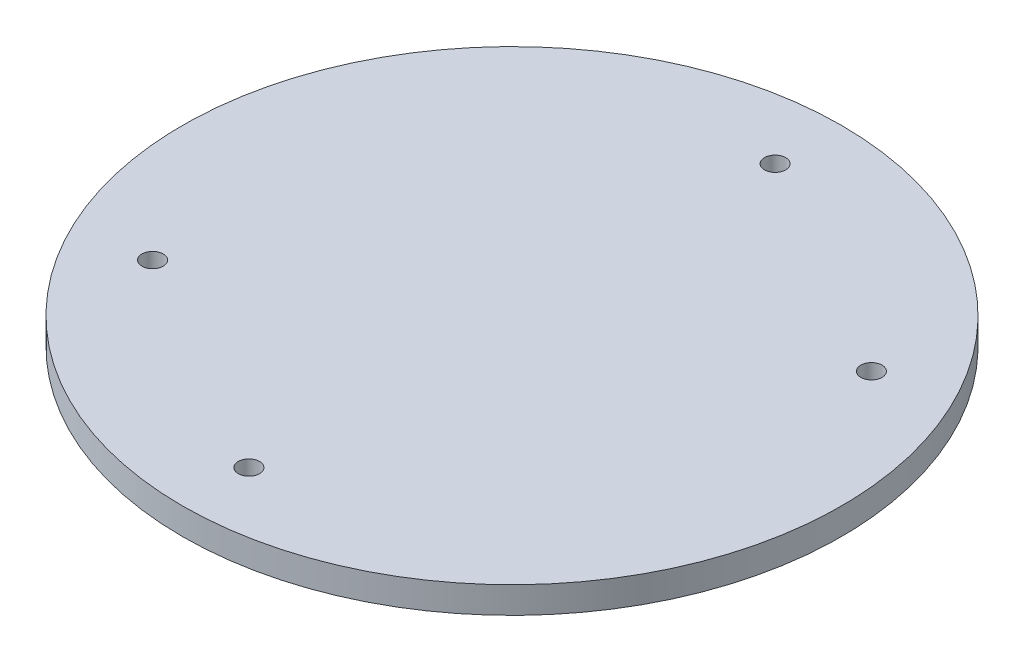
SolidWorks part; units mm, degrees
ref_plane "Front Plane" through (0, 0, 0) normal (0, 0, 1) x (1, 0, 0)
ref_plane "Top Plane" through (0, 0, 0) normal (0, 1, 0) x (1, 0, 0)
ref_plane "Right Plane" through (0, 0, 0) normal (1, 0, 0) x (0, 0, -1)
sketch "Sketch1" plane through (0, 0, 0) normal (0, 1, 0) x (1, 0, 0)
  circle A0 centre (0, 0) radius 62
  dimension "D1" = 124
extrude "Boss-Extrude1" add sketch "Sketch1" along normal blind 5
sketch "Sketch2" plane through (0, 5, 0) normal (0, 1, 0) x (1, 0, 0)
  circle A0 centre (0, 49.5) radius 2
  dimension "D2" = 4
  dimension "D1" = 49.5
extrude "Cut-Extrude1" cut sketch "Sketch2" against normal blind 5 contours A0
pattern_circular "CirPattern1" count 2 every 120 about axis through (0, 5, 0) along (0, 1, 0) of "Cut-Extrude1"
sketch "Sketch4" plane through (0, 5, 0) normal (0, 1, 0) x (1, 0, 0)
  line L0 (0, 49.5) -> (-42.8683, -24.75) construction
  line L1 (0, 0) -> (-23.6703, -40.9981) construction
ref_plane "Plane1" through (0, 0, 0) normal (-0.866, 0, -0.5) x (-0.5, 0, 0.866)
mirror "Mirror1" about plane through (0, 0, 0) normal (-0.866, 0, -0.5) of "Cut-Extrude1", "CirPattern1"
